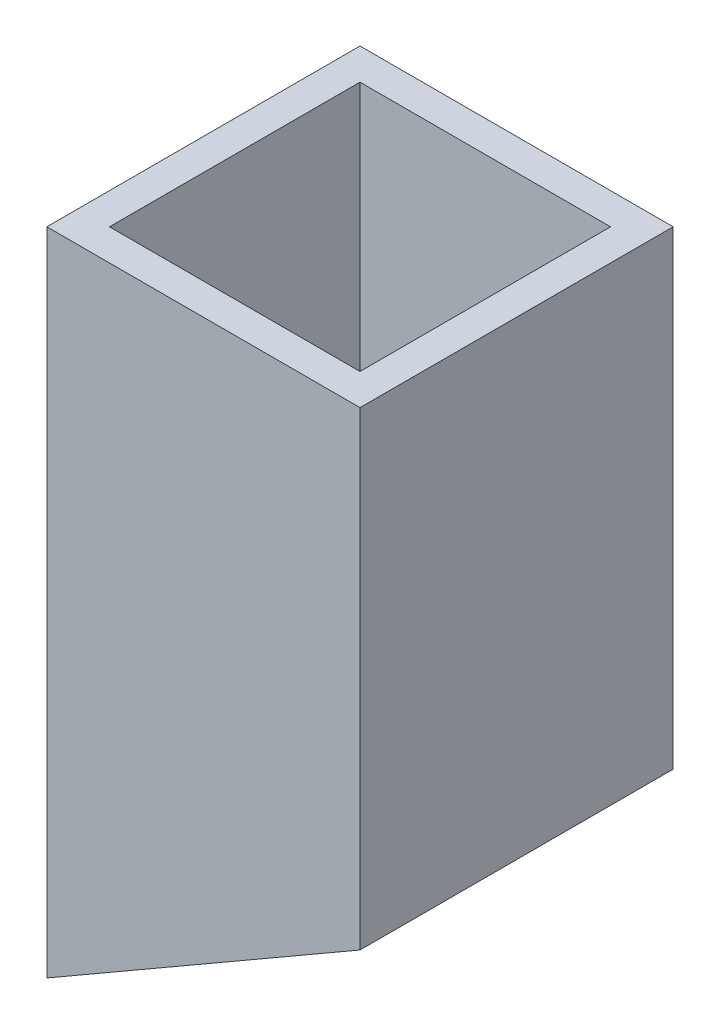
SolidWorks part; units mm, degrees
ref_plane "Alzado" through (0, 0, 0) normal (0, 0, 1) x (1, 0, 0)
ref_plane "Planta" through (0, 0, 0) normal (0, 1, 0) x (1, 0, 0)
ref_plane "Vista lateral" through (0, 0, 0) normal (1, 0, 0) x (0, 0, -1)
sketch "Croquis1" plane through (0, 0, 0) normal (0, 1, 0) x (1, 0, 0)
  line L1 (0, 0) -> (100, 0)
  line L2 (0, 0) -> (0, 100)
  line L3 (0, 100) -> (100, 100)
  line L4 (100, 0) -> (100, 100)
  dimension "D1" = 100
  dimension "D2" = 100
extrude "Saliente-Extruir1" add sketch "Croquis1" along normal blind 150
sketch "Croquis2" plane through (0, 0, 0) normal (0, 0, 1) x (1, 0, 0)
  line L0 (0, 0) -> (0, -57.735)
  line L1 (0, -57.735) -> (100, 0)
  line L2 (100, 0) -> (0, 0)
  dimension "D1" = 30
extrude "Saliente-Extruir2" add sketch "Croquis2" against normal up to surface (100 mm away) up to face at (50, 75, -100)
shell "Vaciado4" thickness 10 removed face at (50, 150, -50)
